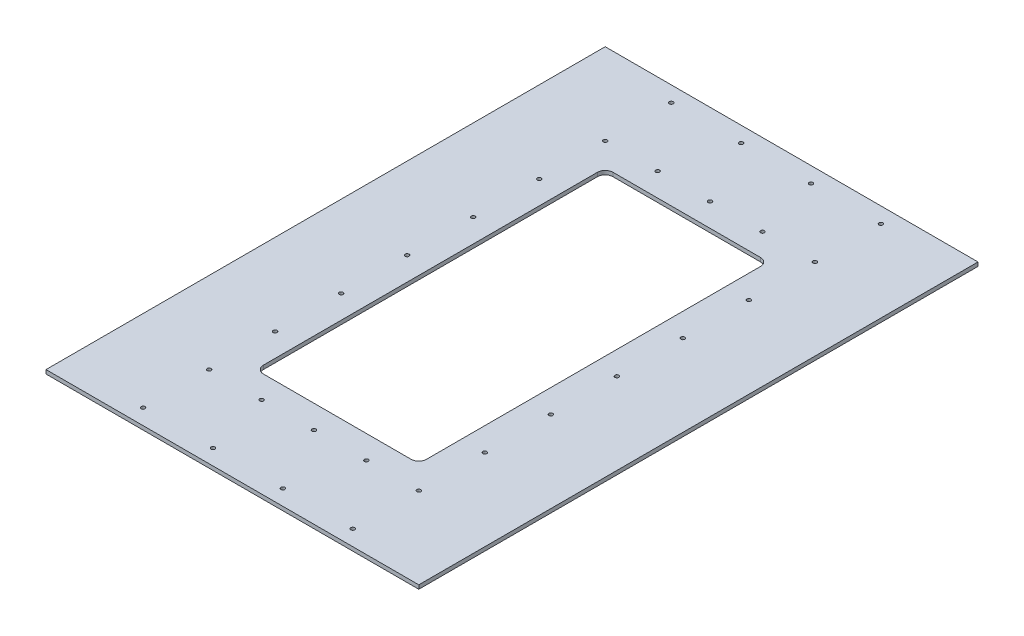
SolidWorks part; units mm, degrees
material "6061 Alloy"
ref_plane "Front Plane" through (0, 0, 0) normal (0, 0, 1) x (1, 0, 0)
ref_plane "Top Plane" through (0, 0, 0) normal (0, 1, 0) x (1, 0, 0)
ref_plane "Right Plane" through (0, 0, 0) normal (1, 0, 0) x (0, 0, -1)
sketch "Sketch1" plane through (0, 609.6, 0) normal (0, 1, 0) x (1, 0, 0)
  line L1 (-304.8, 457.2) -> (304.8, 457.2)
  line L2 (-304.8, 457.2) -> (-304.8, -457.2)
  line L3 (-304.8, -457.2) -> (304.8, -457.2)
  line L4 (304.8, 457.2) -> (304.8, -457.2)
  point P6 (0, 457.2)
  point P7 (-304.8, 0)
  dimension "D1" = 609.6
  dimension "D2" = 914.4
extrude "Boss-Extrude1" add sketch "Sketch1" against normal blind 6.35 separate body
sketch "Sketch2" plane through (0, 609.6, 0) normal (0, 1, 0) x (1, 0, 0)
  line L0 (304.8, 457.2) -> (-304.8, 457.2) construction
  line L1 (-133.35, 285.75) -> (133.35, 285.75)
  line L2 (-133.35, 285.75) -> (-133.35, -285.75)
  line L3 (-133.35, -285.75) -> (133.35, -285.75)
  line L4 (133.35, 285.75) -> (133.35, -285.75)
  line L5 (-304.8, 457.2) -> (-304.8, -457.2) construction
  point P6 (0, 457.2)
  point P7 (0, 285.75)
  point P10 (-304.8, 0)
  point P11 (-133.35, 0)
  dimension "D1" = 266.7
  dimension "D2" = 571.5
extrude "Cut-Extrude1" cut sketch "Sketch2" against normal through all
fillet "Fillet1" radius 12.7 4 edges at (133.35, 606.425, 285.75) (-133.35, 606.425, 285.75) (-133.35, 606.425, -285.75) (133.35, 606.425, -285.75)
sketch "Sketch3" plane through (0, 609.6, 0) normal (0, 1, 0) x (1, 0, 0)
  circle A0 centre (-171.45, 215.9) radius 3.175 construction
  circle A1 centre (-171.45, 107.95) radius 3.175 construction
  circle A2 centre (-171.45, 0) radius 3.175 construction
  circle A3 centre (-171.45, -107.95) radius 3.175 construction
  circle A4 centre (-171.45, -215.9) radius 3.175 construction
  circle A5 centre (-171.45, -323.85) radius 3.175 construction
  circle A6 centre (-85.725, -323.85) radius 3.175 construction
  circle A7 centre (0, -323.85) radius 3.175 construction
  circle A8 centre (85.725, -323.85) radius 3.175 construction
  circle A9 centre (171.45, -323.85) radius 3.175 construction
  circle A10 centre (171.45, -215.9) radius 3.175 construction
  circle A11 centre (171.45, -107.95) radius 3.175 construction
  circle A12 centre (171.45, 0) radius 3.175 construction
  circle A13 centre (171.45, 107.95) radius 3.175 construction
  circle A14 centre (171.45, 215.9) radius 3.175 construction
  circle A15 centre (171.45, 323.85) radius 3.175 construction
  circle A16 centre (85.725, 323.85) radius 3.175 construction
  circle A17 centre (0, 323.85) radius 3.175 construction
  circle A18 centre (-85.725, 323.85) radius 3.175 construction
  circle A19 centre (-171.45, 323.85) radius 3.175 construction
  circle A20 centre (-171.45, 215.9) radius 3.175
  circle A21 centre (-171.45, 107.95) radius 3.175
  circle A22 centre (-171.45, 0) radius 3.175
  circle A23 centre (-171.45, -107.95) radius 3.175
  circle A24 centre (-171.45, -215.9) radius 3.175
  circle A25 centre (-171.45, -323.85) radius 3.175
  circle A26 centre (-85.725, -323.85) radius 3.175
  circle A27 centre (0, -323.85) radius 3.175
  circle A28 centre (85.725, -323.85) radius 3.175
  circle A29 centre (171.45, -323.85) radius 3.175
  circle A30 centre (171.45, -215.9) radius 3.175
  circle A31 centre (171.45, -107.95) radius 3.175
  circle A32 centre (171.45, 0) radius 3.175
  circle A33 centre (171.45, 107.95) radius 3.175
  circle A34 centre (171.45, 215.9) radius 3.175
  circle A35 centre (171.45, 323.85) radius 3.175
  circle A36 centre (85.725, 323.85) radius 3.175
  circle A37 centre (0, 323.85) radius 3.175
  circle A38 centre (-85.725, 323.85) radius 3.175
  circle A39 centre (-171.45, 323.85) radius 3.175
extrude "Cut-Extrude2" cut sketch "Sketch3" against normal through all
sketch "Sketch4" plane through (0, 609.6, 0) normal (0, 1, 0) x (1, 0, 0)
  point P0 (171.45, -431.8)
hole_wizard "1/4 (0.25) Diameter Hole1" positions "Sketch4" profile "Sketch5" hole size "1/4" standard "ANSI Inch" end condition through all
sketch "Sketch5" plane through (171.45, 609.6, 431.8) normal (1, 0, 0) x (0, 0, 1)
  line L0 (0, 0) -> (0, 6.35)
  line L1 (0, 6.35) -> (3.175, 6.35)
  line L2 (3.175, 6.35) -> (3.175, 0)
  line L5 (3.175, 0) -> (0, 0)
  line L11 (0, -6.35) -> (0, 107.95) construction
  dimension "Thru Hole Dia." = 6.35
  dimension "Thru Hole Depth" = 6.35
pattern_linear "LPattern1" count 4 spacing 114.3 along (-1, 0, 0) of "1/4 (0.25) Diameter Hole1"
sketch "Sketch6" plane through (0, 609.6, 0) normal (0, 1, 0) x (1, 0, 0)
  point P0 (-171.45, 431.8)
hole_wizard "1/4 (0.25) Diameter Hole2" positions "Sketch6" profile "Sketch7" hole size "1/4" standard "ANSI Inch" end condition through all
sketch "Sketch7" plane through (-171.45, 609.6, -431.8) normal (1, 0, 0) x (0, 0, 1)
  line L0 (0, 0) -> (0, 6.35)
  line L1 (0, 6.35) -> (3.175, 6.35)
  line L2 (3.175, 6.35) -> (3.175, 0)
  line L5 (3.175, 0) -> (0, 0)
  line L11 (0, -6.35) -> (0, 107.95) construction
  dimension "Thru Hole Dia." = 6.35
  dimension "Thru Hole Depth" = 6.35
pattern_linear "LPattern2" count 4 spacing 114.3 along (1, 0, 0) of "1/4 (0.25) Diameter Hole2"
